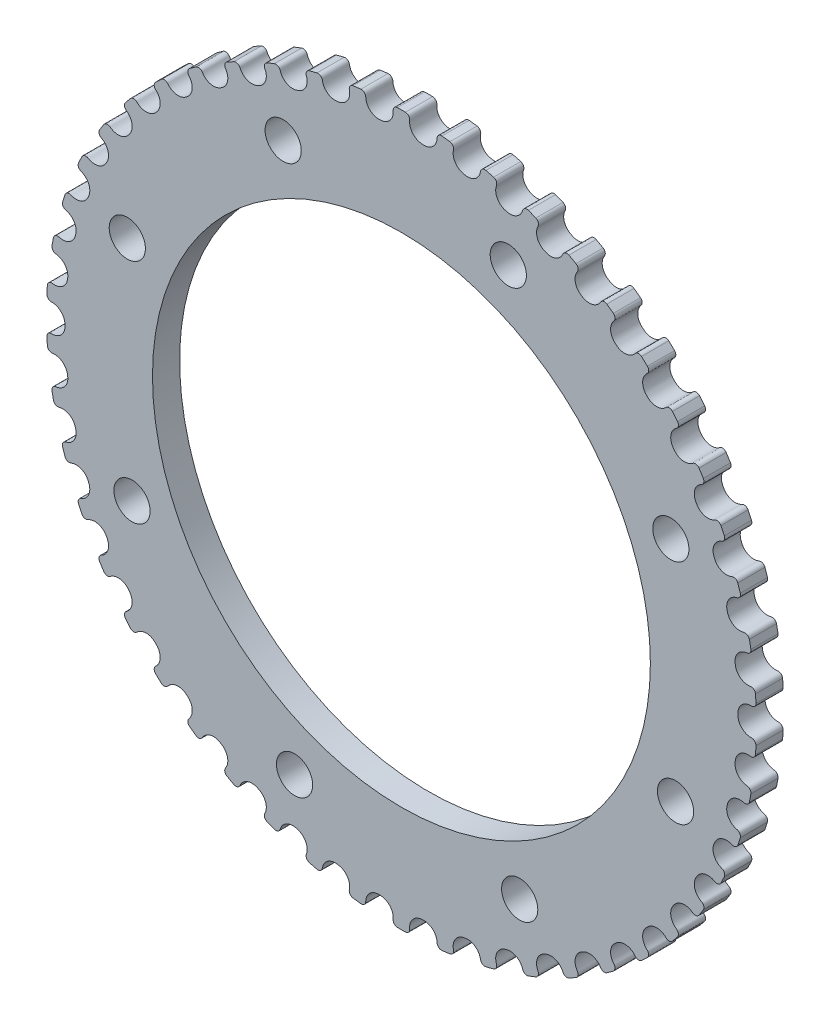
SolidWorks part; units mm, degrees
material "Thornel Mat VMA"
ref_plane "Front Plane" through (0, 0, 0) normal (0, 0, 1) x (1, 0, 0)
ref_plane "Top Plane" through (0, 0, 0) normal (0, 1, 0) x (1, 0, 0)
ref_plane "Right Plane" through (0, 0, 0) normal (1, 0, 0) x (0, 0, -1)
ref_axis "Axis1" through (0, 0, 55) along (0, 0, -1)
sketch "SketchRevolveGearBelt01" plane through (0, 0, 0) normal (1, 0, 0) x (0, 0, -1)
  line L0 (0, 0) -> (1, 0) construction
  line L1 (1.5, 0) -> (1.5, 39.2172)
  line L2 (1.5, 39.2172) -> (-1.5, 39.2172)
  line L3 (-1.5, 39.2172) -> (-1.5, 0)
  line L4 (-1.5, 0) -> (1.5, 0)
  dimension "GearBeltSide1" = 1.5
  dimension "GearBeltOutsideDiameter" = 39.2172
  dimension "GearBeltSide2" = 1.5
revolve "GearBelt01" add sketch "SketchRevolveGearBelt01" angle 360 about L0
sketch "SketchToothGearBelt01" plane through (0, 0, 0) normal (0, 0, 1) x (1, 0, 0)
  arc A0 (39.1647, 2.0323) -> (39.1647, -2.0323) centre (0, 0) cw
  spline S0 degree 3 poles (39.1647, -2.0323) (39.166, -2.006) (39.1649, -1.9663) (39.1569, -1.9141) (39.1478, -1.8755) (39.1356, -1.8378) (39.1204, -1.8013) (39.1023, -1.7661) (39.0814, -1.7324) (39.0578, -1.7006) (39.0317, -1.6708) (39.0033, -1.6432) (38.9728, -1.618) (38.9403, -1.5953) (38.9061, -1.5754) (38.8703, -1.5582) (38.8333, -1.5441) (38.7953, -1.533) (38.7565, -1.525) (38.7172, -1.5201) (38.6658, -1.5185) (38.59, -1.5198) (38.4897, -1.516) (38.3775, -1.5026) (38.2667, -1.4805) (38.158, -1.4498) (38.052, -1.4107) (37.9494, -1.3633) (37.8509, -1.3081) (37.7569, -1.2453) (37.6682, -1.1753) (37.5853, -1.0986) (37.5086, -1.0156) (37.4387, -0.9268) (37.376, -0.8329) (37.3208, -0.7343) (37.2735, -0.6317) (37.2344, -0.5257) (37.2037, -0.4169) (37.1817, -0.3061) (37.1683, -0.1939) (37.1652, -0.1051) (37.1655, -0.0405) (37.1655, 0) (37.1655, 0.0405) (37.1652, 0.1051) (37.1683, 0.1939) (37.1817, 0.3061) (37.2037, 0.4169) (37.2344, 0.5257) (37.2735, 0.6317) (37.3208, 0.7343) (37.376, 0.8329) (37.4387, 0.9268) (37.5086, 1.0156) (37.5853, 1.0986) (37.6682, 1.1753) (37.7569, 1.2453) (37.8509, 1.3081) (37.9494, 1.3633) (38.052, 1.4107) (38.158, 1.4498) (38.2667, 1.4805) (38.3775, 1.5026) (38.4897, 1.516) (38.59, 1.5198) (38.6658, 1.5185) (38.7172, 1.5201) (38.7565, 1.525) (38.7953, 1.533) (38.8333, 1.5441) (38.8703, 1.5582) (38.9061, 1.5754) (38.9403, 1.5953) (38.9728, 1.618) (39.0033, 1.6432) (39.0317, 1.6708) (39.0578, 1.7006) (39.0814, 1.7324) (39.1023, 1.7661) (39.1204, 1.8013) (39.1356, 1.8378) (39.1478, 1.8755) (39.1569, 1.9141) (39.1649, 1.9663) (39.166, 2.006) (39.1647, 2.0323) knots 0 0 0 0 0.012346 0.01852 0.024693 0.030866 0.037039 0.043212 0.049386 0.055559 0.061732 0.067905 0.074078 0.080252 0.086425 0.092598 0.098771 0.104944 0.111118 0.117291 0.123464 0.135171 0.152781 0.17039 0.188 0.205609 0.223219 0.240828 0.258438 0.276048 0.293657 0.311267 0.328876 0.346486 0.364095 0.381705 0.399315 0.416924 0.434534 0.452143 0.469753 0.487362 0.493681 0.5 0.506319 0.512638 0.530247 0.547857 0.565466 0.583076 0.600685 0.618295 0.635905 0.653514 0.671124 0.688733 0.706343 0.723952 0.741562 0.759172 0.776781 0.794391 0.812 0.82961 0.847219 0.864829 0.876536 0.882709 0.888882 0.895056 0.901229 0.907402 0.913575 0.919748 0.925922 0.932095 0.938268 0.944441 0.950614 0.956788 0.962961 0.969134 0.975307 0.98148 0.987654 1 1 1 1
extrude "ToothExtrudeCutGearBelt01" cut sketch "SketchToothGearBelt01" against normal blind 7.239 and the other way blind 7.239
pattern_circular "PatternGearBelt01" count 50 every 7.2 about axis through (0, 0, 55) along (0, 0, -1) of "ToothExtrudeCutGearBelt01"
sketch "BoreRevolveSketch" plane through (0, 0, 0) normal (1, 0, 0) x (0, 0, -1)
  line L0 (0, 0) -> (1, 0) construction
  line L1 (-7.239, 0) -> (7.239, 0)
  line L2 (7.239, 0) -> (7.239, 27.5)
  line L3 (7.239, 27.5) -> (-7.239, 27.5)
  line L4 (-7.239, 27.5) -> (-7.239, 0)
  dimension "BoreSide1" = 7.239
  dimension "TaperSide1" = 27.5
  dimension "BoreSide2" = 7.239
  dimension "TaperSide2" = 27.5
revolve "BoreRevolveCut" cut sketch "BoreRevolveSketch" angle 360 about L0
sketch "AuxiliarySketchGearBelt01" plane through (0, 0, 0) normal (0, 0, 1) x (1, 0, 0)
  circle A0 centre (0, 0) radius 39.7887 construction
  dimension "PitchDiameter" = 79.5774
sketch "Sketch1" plane through (0, 0, 1.5) normal (0, 0, 1) x (1, 0, 0)
  circle A0 centre (-29.7589, -13.0636) radius 2 construction
  circle A1 centre (-11.8053, -30.2801) radius 2 construction
  circle A2 centre (13.0636, -29.7589) radius 2 construction
  circle A3 centre (30.2801, -11.8053) radius 2 construction
  circle A4 centre (29.7589, 13.0636) radius 2 construction
  circle A5 centre (11.8053, 30.2801) radius 2 construction
  circle A6 centre (-13.0636, 29.7589) radius 2 construction
  circle A7 centre (-30.2801, 11.8053) radius 2 construction
  circle A8 centre (-29.7589, -13.0636) radius 2
  circle A9 centre (-11.8053, -30.2801) radius 2
  circle A10 centre (13.0636, -29.7589) radius 2
  circle A11 centre (30.2801, -11.8053) radius 2
  circle A12 centre (29.7589, 13.0636) radius 2
  circle A13 centre (11.8053, 30.2801) radius 2
  circle A14 centre (-13.0636, 29.7589) radius 2
  circle A15 centre (-30.2801, 11.8053) radius 2
extrude "Cut-Extrude1" cut sketch "Sketch1" against normal blind 10
